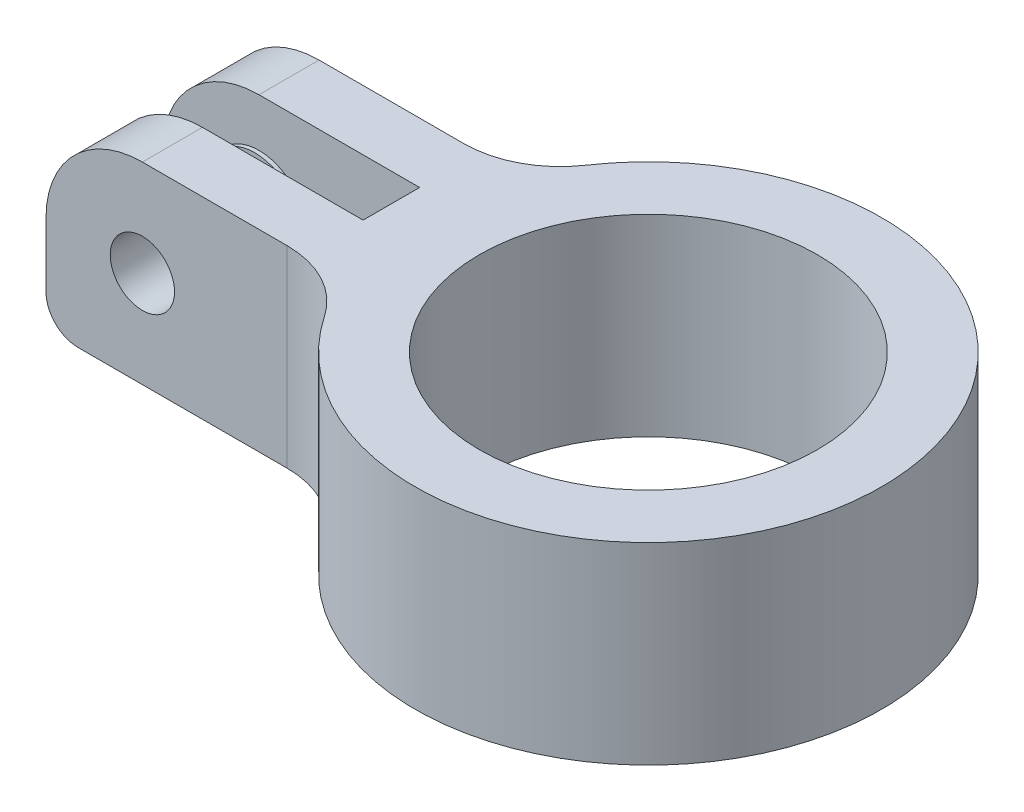
SolidWorks part; units mm, degrees
material "ABS PC"
ref_plane "Front Plane" through (0, 0, 0) normal (0, 0, 1) x (1, 0, 0)
ref_plane "Top Plane" through (0, 0, 0) normal (0, 1, 0) x (1, 0, 0)
ref_plane "Right Plane" through (0, 0, 0) normal (1, 0, 0) x (0, 0, -1)
sketch "Sketch1" plane through (0, 0, 0) normal (0, 1, 0) x (1, 0, 0)
  line L0 (-50.8, 8.7312) -> (-50.8, 2.794)
  line L1 (-21.3329, 8.7312) -> (-50.8, 8.7312)
  line L3 (-21.3329, -8.7312) -> (-50.8, -8.7312)
  line L5 (-50.8, 2.794) -> (-25.4, 2.794)
  line L6 (-25.4, 2.794) -> (-25.4, -2.794)
  line L7 (-25.4, -2.794) -> (-50.8, -2.794)
  line L8 (-50.8, -2.794) -> (-50.8, -8.7312)
  line L9 (-41.275, 8.7312) -> (-41.275, -8.7312) construction
  circle A0 centre (0, 0) radius 16.7005
  circle A1 centre (0, 0) radius 23.0505
  dimension "D1" = 33.401
  dimension "D2" = 6.35
  dimension "D3" = 25.4
  dimension "D4" = 17.4625
  dimension "D5" = 5.588
  dimension "D6" = 15.875
  dimension "D7" = 9.525
extrude "Boss-Extrude1" add sketch "Sketch1" along normal blind 19.05 contours L1 L9 L5 L6 L7 L3 A1 | A1 A0 | L9 L7 L8 L3 | L9 L1 L0 L5 region at (-46.0375, 0, -5.7626) region at (-31.3039, 0, -8.4662) region at (4.3235, 0, -21.9773) region at (-46.0375, 0, 5.7626)
sketch "Sketch2" plane through (0, 0, 8.7312) normal (0, 0, 1) x (1, 0, 0)
  line L1 (-50.8, 19.05) -> (-50.8, 0) construction
  circle A0 centre (-41.275, 9.525) radius 3.175
  circle A1 centre (-41.275, 9.525) radius 4.7625
  point P7 (-50.8, 9.525)
  dimension "D1" = 6.35
  dimension "D2" = 9.525
  dimension "D3" = 9.525
extrude "Cut-Extrude1" cut sketch "Sketch2" against normal through all contours A0 region at (-41.275, 9.525, 8.7312)
extrude "Boss-Extrude2" add sketch "Sketch2<3>" against normal blind 6.35
sketch "Sketch2<3>" plane through (0, 0, 8.7312) normal (0, 0, 1) x (1, 0, 0) same geometry as "Sketch2"
mirror "Mirror1" about plane through (0, 0, 0) normal (0, 0, 1) of "Boss-Extrude2"
fillet "Fillet1" radius 9.525 4 edges at (-21.3329, 9.525, 8.7312) (-21.3329, 9.525, -8.7312) (-50.8, 19.05, -5.7626) (-50.8, 19.05, 5.7626)
fillet "Fillet2" radius 3.175 2 edges at (-50.8, 0, 5.7626) (-50.8, 0, -5.7626)
